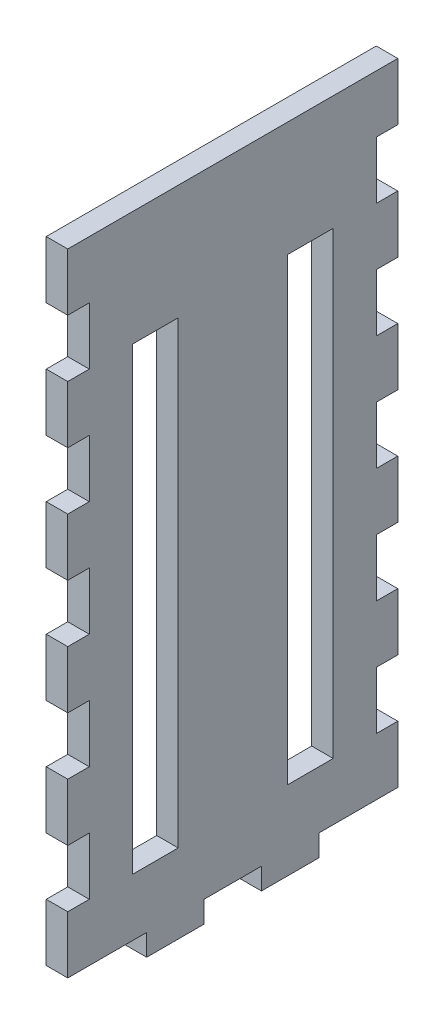
SolidWorks part; units mm, degrees
ref_plane "Front Plane" through (0, 0, 0) normal (0, 0, 1) x (1, 0, 0)
ref_plane "Top Plane" through (0, 0, 0) normal (0, 1, 0) x (1, 0, 0)
ref_plane "Right Plane" through (0, 0, 0) normal (1, 0, 0) x (0, 0, -1)
sketch "Sketch1" plane through (0, 0, 0) normal (1, 0, 0) x (0, 0, -1)
  line L1 (-63.5, -139.7) -> (63.5, -139.7)
  line L2 (-63.5, -139.7) -> (-63.5, 139.7)
  line L3 (-63.5, 139.7) -> (63.5, 139.7)
  line L4 (63.5, -139.7) -> (63.5, 139.7)
  line L5 (-63.5, -139.7) -> (63.5, 139.7) construction
  line L6 (-63.5, 139.7) -> (63.5, -139.7) construction
  point P0 (0, 0)
  dimension "D1" = 127
  dimension "D2" = 279.4
extrude "Boss-Extrude1" add sketch "Sketch1" along normal blind 9.525
sketch "Sketch2" plane through (0, 0, 63.5) normal (0, 0, 1) x (1, 0, 0)
  line L0 (0, 139.7) -> (0, -139.7) construction
  line L1 (0, 139.7) -> (9.525, 139.7)
  line L2 (0, 139.7) -> (0, 114.3)
  line L3 (0, 114.3) -> (9.525, 114.3)
  line L4 (9.525, 139.7) -> (9.525, 114.3)
  line L5 (0, -69.85) -> (0, 69.85) construction
  line L6 (9.525, 139.7) -> (9.525, -139.7) construction
  line L7 (9.525, 139.7) -> (0, 139.7) construction
  dimension "D1" = 25.4
  dimension "D2" = 0
extrude "Boss-Extrude2" add sketch "Sketch2" along normal blind 9.525
pattern_linear "LPattern1" count 6 spacing 50.8 along (0, -1, 0) of "Boss-Extrude2"
mirror "Mirror1" about plane through (0, 0, 0) normal (0, 0, 1) of "LPattern1"
sketch "Sketch3" plane through (0, -139.7, 0) normal (0, -1, 0) x (1, 0, 0)
  line L0 (0, 73.025) -> (0, -73.025) construction
  line L1 (0, 38.1) -> (9.525, 38.1)
  line L2 (0, 38.1) -> (0, 12.7)
  line L3 (0, 12.7) -> (9.525, 12.7)
  line L4 (9.525, 38.1) -> (9.525, 12.7)
  line L5 (9.525, 73.025) -> (9.525, -73.025) construction
  line L6 (0, 73.025) -> (9.525, 73.025) construction
  dimension "D1" = 34.925
  dimension "D2" = 25.4
extrude "Boss-Extrude3" add sketch "Sketch3" along normal blind 9.525
pattern_linear "LPattern2" count 2 spacing 50.8 along (0, 0, -1) of "Boss-Extrude3"
sketch "Sketch4" plane through (9.525, 0, 0) normal (1, 0, 0) x (0, 0, -1)
  line L1 (-44.45, -114.3) -> (-24.13, -114.3)
  line L3 (-44.45, 88.9) -> (-24.13, 88.9)
  line L5 (-73.025, -139.7) -> (-38.1, -139.7) construction
  line L6 (-73.025, 88.9) -> (-63.5, 88.9) construction
  line L7 (-24.13, -114.3) -> (-24.13, 88.9)
  line L8 (-44.45, -114.3) -> (-44.45, 88.9)
  line L9 (0, -139.7) -> (0, 139.7) construction
  line L10 (-12.7, -139.7) -> (12.7, -139.7) construction
  line L11 (73.025, 139.7) -> (-73.025, 139.7) construction
  point P10 (-68.2625, 88.9)
  dimension "D1" = 24.13
  dimension "D2" = 20.32
  dimension "D3" = 25.4
  dimension "D4" = 0
extrude "Cut-Extrude1" cut sketch "Sketch4" against normal blind 9.525
mirror "Mirror2" about plane through (0, 0, 0) normal (0, 0, 1) of "Cut-Extrude1"
sketch "Sketch5" plane through (0, 0, 0) normal (-1, 0, 0) x (0, 0, 1)
  circle A0 centre (-1.775, 53.4964) radius 2.5 construction
  circle A1 centre (-1.775, 53.4964) radius 2.5
  circle A2 centre (-1.775, 34.9964) radius 2.5 construction
  circle A3 centre (-1.775, 34.9964) radius 2.5
  circle A4 centre (1.775, 19.4604) radius 2.5 construction
  circle A5 centre (1.775, 19.4604) radius 2.5
  circle A6 centre (1.775, 0.9604) radius 2.5 construction
  circle A7 centre (1.775, 0.9604) radius 2.5
  circle A8 centre (-1.775, -16.5756) radius 2.5 construction
  circle A9 centre (-1.775, -16.5756) radius 2.5
  circle A10 centre (-1.775, -35.0756) radius 2.5 construction
  circle A11 centre (-1.775, -35.0756) radius 2.5
  circle A12 centre (1.775, -50.3156) radius 2.5 construction
  circle A13 centre (1.775, -50.3156) radius 2.5
  circle A14 centre (1.775, -68.8156) radius 2.5 construction
  circle A15 centre (1.775, -68.8156) radius 2.5
